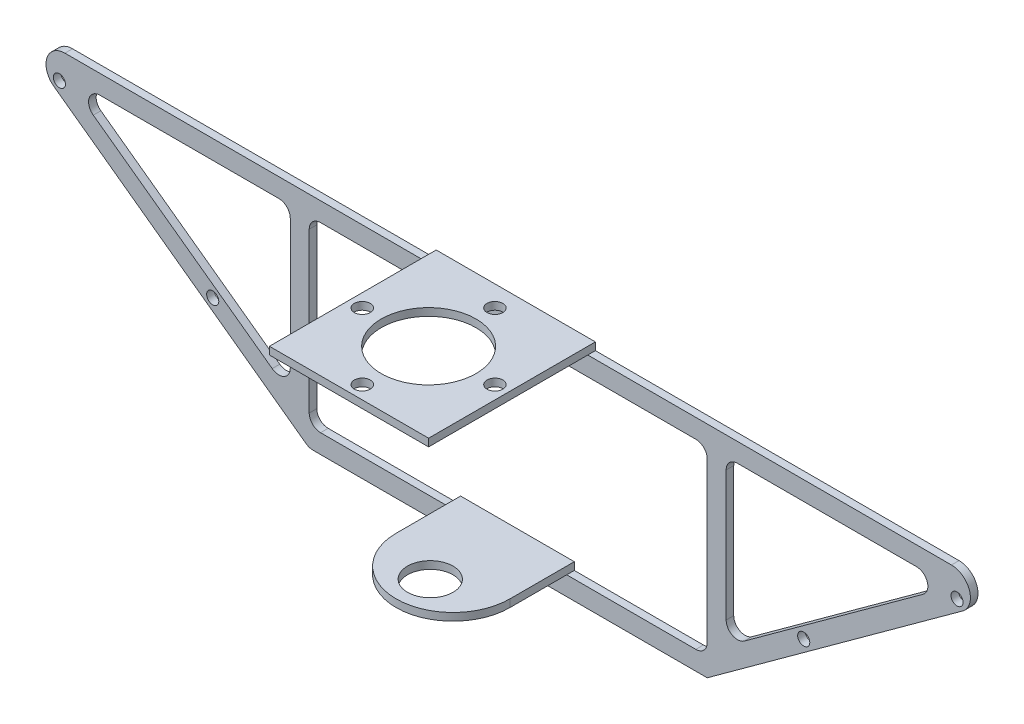
SolidWorks part; units mm, degrees
material "6061 合金"
ref_plane "正面" through (0, 0, 0) normal (0, 0, 1) x (1, 0, 0)
ref_plane "平面" through (0, 0, 0) normal (0, 1, 0) x (1, 0, 0)
ref_plane "右側面" through (0, 0, 0) normal (1, 0, 0) x (0, 0, -1)
sketch "ｽｹｯﾁ1" plane through (0, 0, 0) normal (0, 0, 1) x (1, 0, 0)
  line L0 (-116.9417, 29) -> (116.9417, 29)
  line L1 (52.5, -24) -> (-52.5, -24)
  line L2 (52.5, -24) -> (52.5, 24)
  line L3 (52.5, 24) -> (-52.5, 24)
  line L4 (-52.5, -24) -> (-52.5, 24)
  line L5 (52.5, -24) -> (-52.5, 24) construction
  line L6 (52.5, 24) -> (-52.5, -24) construction
  line L7 (119.8807, 19.9549) -> (52.5, -29)
  line L8 (52.5, -29) -> (-52.5, -29)
  line L9 (-52.5, -29) -> (-119.8807, 19.9549)
  line L10 (-128.0769, 29) -> (-48.2467, -29) construction
  line L11 (0, 29) -> (0, -29) construction
  line L12 (128.0769, 29) -> (48.2467, -29) construction
  line L13 (-116.9417, 24) -> (-119.8807, 19.9549) construction
  line L14 (116.9417, 24) -> (119.8807, 19.9549) construction
  line L15 (-57.5, 21) -> (-57.5, -13.2991)
  line L16 (-62.2634, -15.7262) -> (-116.9417, 24)
  line L17 (-116.9417, 24) -> (-60.5, 24)
  line L18 (62.2634, -15.7262) -> (116.9417, 24)
  line L19 (57.5, 21) -> (57.5, -13.2991)
  line L20 (116.9417, 24) -> (60.5, 24)
  arc A0 (116.9417, 29) -> (119.8807, 19.9549) centre (116.9417, 24) cw
  arc A1 (-116.9417, 29) -> (-119.8807, 19.9549) centre (-116.9417, 24) ccw
  circle A2 centre (118.4112, 21.9775) radius 1.6
  circle A3 centre (77.9603, -7.4118) radius 1.6
  circle A4 centre (-118.4112, 21.9775) radius 1.6
  circle A5 centre (-77.9603, -7.4118) radius 1.6
  arc A6 (-57.5, -13.2991) -> (-62.2634, -15.7262) centre (-60.5, -13.2991) cw
  arc A7 (-57.5, 21) -> (-60.5, 24) centre (-60.5, 21) ccw
  arc A8 (57.5, -13.2991) -> (62.2634, -15.7262) centre (60.5, -13.2991) ccw
  arc A9 (57.5, 21) -> (60.5, 24) centre (60.5, 21) cw
  point P0 (0, 0)
  dimension "D7" = 5
  dimension "D8" = 50
  dimension "D9" = 3.2
  dimension "D12" = 3
  dimension "D1" = 105
  dimension "D2" = 48
  dimension "D3" = 5
  dimension "D4" = 5
  dimension "D5" = 54
  dimension "D6" = 2.5
  dimension "D10" = 5
  dimension "D11" = 5
extrude "ﾎﾞｽ - 押し出し1" add sketch "ｽｹｯﾁ1" along normal blind 2
fillet "ﾌｨﾚｯﾄ1" radius 3 7 edges at (116.9417, 24, 1) (52.5, -24, 1) (52.5, 24, 1) (-52.5, -29, 1) (-52.5, -24, 1) (-52.5, 24, 1) (-116.9417, 24, 1)
sketch "ｽｹｯﾁ2" plane through (0, 0, 0) normal (0, 0, -1) x (-1, 0, 0)
  line L0 (49.5, -24) -> (-49.5, -24) construction
  line L1 (14.563, -22) -> (-15.437, -22)
  line L2 (14.563, -22) -> (14.563, -24)
  line L3 (14.563, -24) -> (-15.437, -24)
  line L4 (-15.437, -22) -> (-15.437, -24)
  line L5 (14.563, -22) -> (-15.437, -24) construction
  line L6 (14.563, -24) -> (-15.437, -22) construction
  line L7 (0, 29) -> (-0.4874, -29) construction
  line L8 (-116.9417, 29) -> (116.9417, 29) construction
  line L9 (51.5252, -29) -> (-52.5, -29) construction
  point P0 (-0.437, -23)
  dimension "D1" = 2
  dimension "D2" = 30
extrude "ﾎﾞｽ - 押し出し2" add sketch "ｽｹｯﾁ2" against normal blind 32
sketch "ｽｹｯﾁ3" plane through (0, -24, 0) normal (0, -1, 0) x (1, 0, 0)
  line L0 (0.437, 32) -> (0.437, 2) construction
  line L1 (15.437, 32) -> (15.437, 2) construction
  line L2 (-14.563, 17) -> (-14.563, 32)
  line L7 (-14.563, 32) -> (15.437, 32)
  line L8 (15.437, 32) -> (-14.563, 32) construction
  line L9 (-14.563, 2) -> (15.437, 2) construction
  line L10 (15.437, 32) -> (15.437, 17)
  line L11 (-14.563, 32) -> (-14.563, 2) construction
  arc A2 (-14.563, 17) -> (15.437, 17) centre (0.437, 17) cw
  circle A3 centre (0.437, 23) radius 6
  line M1 (-14.563, 32) -> (-14.563, 2)
  line M3 (15.437, 2) -> (15.437, 32)
  line M4 (15.437, 32) -> (-14.563, 32)
  dimension "D1" = 15
  dimension "D2" = 12
  dimension "D3" = 21
extrude "ｶｯﾄ - 押し出し1" cut sketch "ｽｹｯﾁ3" against normal up to next contours A2 L7 M1 | L0 A3 | A3 L0 | A2 M4 M3 region at (2.9834, -24, 23) region at (-2.1095, -24, 23) region at (-11.2125, -24, 28.6495) region at (12.0864, -24, 28.6495)
sketch "ｽｹｯﾁ4" plane through (0, 0, 0) normal (0, 0, -1) x (-1, 0, 0)
  line L0 (-116.9417, 29) -> (116.9417, 29) construction
  line L1 (21, 31) -> (-21, 31)
  line L2 (21, 31) -> (21, 29)
  line L3 (21, 29) -> (-21, 29)
  line L4 (-21, 31) -> (-21, 29)
  line L5 (21, 31) -> (-21, 29) construction
  line L6 (21, 29) -> (-21, 31) construction
  line L7 (0, 24) -> (0, 0) construction
  line L8 (-49.5, 24) -> (49.5, 24) construction
  point P0 (0, 30)
  dimension "D1" = 2
  dimension "D2" = 42
extrude "ﾎﾞｽ - 押し出し3" add sketch "ｽｹｯﾁ4" against normal blind 44
sketch "ｽｹｯﾁ5" plane through (0, 31, 0) normal (0, 1, 0) x (1, 0, 0)
  line L0 (0, 0) -> (0, -44) construction
  line L1 (-21, -44) -> (21, -44) construction
  line L2 (-21, -23) -> (21, -23) construction
  line L3 (-21, -44) -> (-21, 0) construction
  line L4 (21, -44) -> (21, 0) construction
  line L5 (-21, -2) -> (-116.9417, -2) construction
  circle A0 centre (0, -5.5) radius 2.1
  circle A1 centre (-17.5, -23) radius 2.1
  circle A2 centre (0, -40.5) radius 2.1
  circle A3 centre (17.5, -23) radius 2.1
  circle A4 centre (0, -23) radius 12.5
  point P15 (0, -7.6)
  point P16 (0, -7.6)
  point P17 (0, -23)
  point P27 (0, -23)
  dimension "D2" = 17.5
  dimension "D3" = 4.2
  dimension "D5" = 25
  dimension "D1" = 21
  dimension "D4" = 4
extrude "ｶｯﾄ - 押し出し2" cut sketch "ｽｹｯﾁ5" against normal up to next and the other way through all
